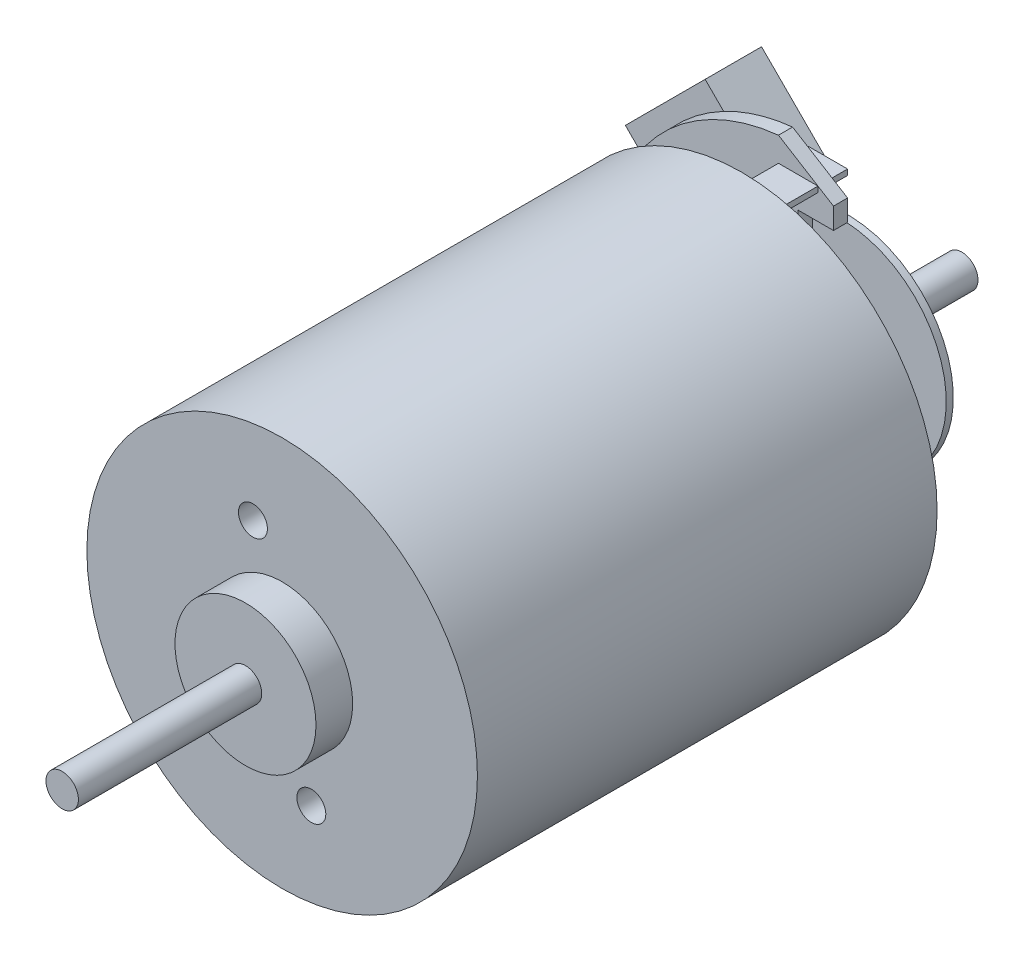
SolidWorks part; units mm, degrees
ref_plane "Front" through (0, 0, 0) normal (0, 0, 1) x (1, 0, 0)
ref_plane "Top" through (0, 0, 0) normal (0, 1, 0) x (1, 0, 0)
ref_plane "Right" through (0, 0, 0) normal (1, 0, 0) x (0, 0, -1)
sketch "Sketch1" plane through (0, 0, 0) normal (0, 0, 1) x (1, 0, 0)
  circle A0 centre (0, 0) radius 13.85
  dimension "D1" = 27.7
extrude "MAINBODY" add sketch "Sketch1" along normal blind 16.3 and the other way blind 16.3
sketch "Sketch2" plane through (0, 0, 16.3) normal (0, 0, 1) x (1, 0, 0)
  circle A0 centre (0, 0) radius 5
  circle A1 centre (0, 0) radius 1.15
  dimension "D1" = 10
  dimension "D2" = 2.3
extrude "OUTPUTSHAFT" add sketch "Sketch2" along normal blind 15.6 contours A1 region at (0, 0, 16.3)
extrude "OUTPUTBOSS" add sketch "Sketch2<3>" along normal blind 2.6 contours A0 A1 region at (-4.8586, 0, 16.3)
sketch "Sketch2<3>" plane through (0, 0, 16.3) normal (0, 0, 1) x (1, 0, 0) same geometry as "Sketch2"
hole_wizard "M2.5x0.45 Tapped Hole1" positions "Sketch7" profile "Sketch6" tap size "M2.5x0.45" standard "ANSI Metric"
sketch "Sketch7" plane through (0, 0, 16.3) normal (0, 0, 1) x (1, 0, 0)
  line L0 (-2.0706, 7.7274) -> (2.0706, -7.7274) construction
  line L1 (0, 0) -> (0, 13.85) construction
  circle A0 centre (0, 0) radius 13.85 construction
  point P0 (-2.0706, 7.7274)
  point P2 (2.0706, -7.7274)
  dimension "D1" = 15
  dimension "D2" = 16
sketch "Sketch6" plane through (-2.0706, 7.7274, 16.3) normal (1, 0, 0) x (0, -1, 0)
  line L0 (0, 0) -> (0, 6.9659)
  line L1 (0, 6.9659) -> (1.025, 6.35)
  line L2 (1.025, 6.35) -> (1.025, 0)
  line L5 (1.025, 0) -> (0, 0)
  line L10 (0, 6.9659) -> (-1.025, 6.35) construction
  line L11 (0, -6.35) -> (0, 107.95) construction
  dimension "Tap Drill Dia." = 2.05
  dimension "Tap Drill Depth" = 6.35
  dimension "Drill Angle" = 118
cosmetic thread "Hole Thread1" parameters "D1"=5, "D2"=2.5
cosmetic thread "Hole Thread2" parameters "D1"=5, "D2"=2.5
mirror "REARSHAFT" about plane through (0, 0, 0) normal (0, 0, 1) of "OUTPUTBOSS", "OUTPUTSHAFT"
sketch "Sketch5" plane through (0, 0, -16.3) normal (0, 0, -1) x (-1, 0, 0)
  line L0 (0, 13.85) -> (0, -13.85) construction
  line L2 (-1.4, 11.3) -> (1.4, 11.3)
  line L3 (-1.4, 11.3) -> (-1.4, 11.7)
  line L4 (-1.4, 11.7) -> (1.4, 11.7)
  line L5 (1.4, 11.3) -> (1.4, 11.7)
  line L6 (-1.4, 11.3) -> (1.4, 11.7) construction
  line L7 (-1.4, 11.7) -> (1.4, 11.3) construction
  line L8 (-1.4, -11.7) -> (1.4, -11.7)
  line L9 (-1.4, -11.7) -> (-1.4, -11.3)
  line L10 (-1.4, -11.3) -> (1.4, -11.3)
  line L11 (1.4, -11.7) -> (1.4, -11.3)
  line L12 (-1.4, -11.7) -> (1.4, -11.3) construction
  line L13 (-1.4, -11.3) -> (1.4, -11.7) construction
  circle A0 centre (0, 0) radius 13.85 construction
  point P5 (0, 11.5)
  point P10 (0, -11.5)
  dimension "D1" = 11.3
  dimension "D2" = 11.3
  dimension "D3" = 0.4
  dimension "D4" = 2.8
extrude "TERMINALS" add sketch "Sketch5" along normal blind 6.1
sketch "Sketch8" plane through (0, 0, -16.3) normal (0, 0, -1) x (-1, 0, 0)
  line L0 (1.4, 13.4272) -> (-2.5, 11.0215)
  line L1 (-2.5, 11.0215) -> (-2.5, 9.5215)
  line L2 (-2.5, 9.5215) -> (0, 9.5215)
  line L3 (0, 9.5215) -> (0, 5)
  line L4 (-5, 0) -> (5, 0) construction
  line L5 (1.4, -13.4272) -> (-2.5, -11.0215)
  line L6 (-2.5, -11.0215) -> (-2.5, -9.5215)
  line L7 (-2.5, -9.5215) -> (0, -9.5215)
  line L8 (0, -9.5215) -> (0, -5)
  line L9 (0, 5) -> (0, -5) construction
  arc A0 (1.4, 13.4272) -> (1.4, -13.4272) centre (0, 0) cw
  arc A1 (0, -5) -> (0, 5) centre (0, 0) ccw
  circle A2 centre (0, 0) radius 5 construction
  circle A3 centre (0, 0) radius 5 construction
  dimension "D1" = 13.5
  dimension "D2" = 1.5
  dimension "D3" = 2.5
extrude "PCB" add sketch "Sketch8" along normal blind 1 from offset 4
sketch "Sketch9" plane through (0, 0, -16.3) normal (0, 0, -1) x (-1, 0, 0)
  circle A0 centre (0, 0) radius 7.5
  dimension "D1" = 15
extrude "ENCODER" add sketch "Sketch9" along normal blind 0.5 from offset 7
sketch "Sketch10" plane through (0, 0, -21.3) normal (0, 0, -1) x (-1, 0, 0)
  line L0 (2.6514, 8.3088) -> (8.3083, 2.6519)
  line L1 (2.6514, 8.3088) -> (7.6011, 13.2585)
  line L2 (8.3083, 2.6519) -> (13.258, 7.6017)
  line L3 (7.6011, 13.2585) -> (13.258, 7.6017)
  line L4 (1.4, 11.7) -> (1.4, 11.3) construction
  dimension "D1" = 7
  dimension "D2" = 8
  dimension "D3" = 3
  dimension "D4" = 45
  dimension "D5" = 7.75
extrude "CONNECTOR" add sketch "Sketch10" along normal blind 4 contours L1 L3 L2 L0
